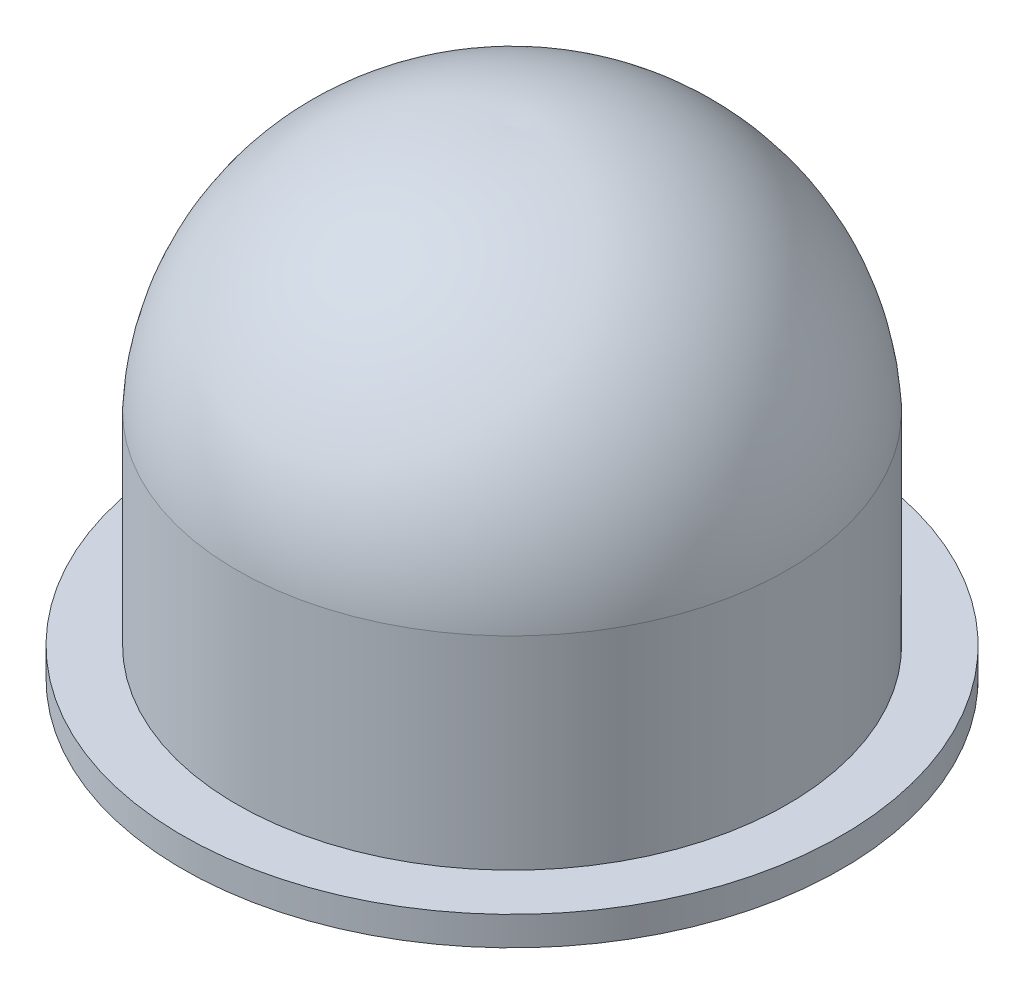
SolidWorks part; units mm, degrees
ref_plane "Front Plane" through (0, 0, 0) normal (0, 0, 1) x (1, 0, 0)
ref_plane "Top Plane" through (0, 0, 0) normal (0, 1, 0) x (1, 0, 0)
ref_plane "Right Plane" through (0, 0, 0) normal (1, 0, 0) x (0, 0, -1)
sketch "Sketch1" plane through (0, 0, 0) normal (0, 0, 1) x (1, 0, 0)
  line L0 (0, 16.6429) -> (0, 0.8) construction
  line L1 (6.8, 0.8) -> (3, 0.8)
  line L2 (-2.5702, 0) -> (11.8346, 0) construction
  line L3 (3, 0) -> (9.093, 0)
  line L4 (9.093, 0) -> (9.093, 0.8)
  line L5 (9.093, 0.8) -> (7.6, 0.8)
  line L6 (7.6, 0.8) -> (7.6, 6.3969)
  line L7 (6.8, 0.8) -> (6.8, 6.3969)
  line L8 (3, 0.8) -> (3, 0)
  line L9 (0, 0) -> (0, -22.417) construction
  line L10 (0, 12.6123) -> (0, 13.2031)
  arc A0 (6.8, 6.3969) -> (0, 12.6123) centre (0.2923, 6.1046) ccw
  arc A1 (7.6, 6.3969) -> (0, 13.2031) centre (0.3969, 6) ccw
  dimension "D1" = 0.8
  dimension "D2" = 0.8
  dimension "D3" = 9.093
  dimension "D4" = 3
  dimension "D5" = 7.6
  dimension "D8" = 0.2923
  dimension "D9" = 0.3969
  dimension "D10" = 6
revolve "Revolve1" add sketch "Sketch1" angle 360 about L0
